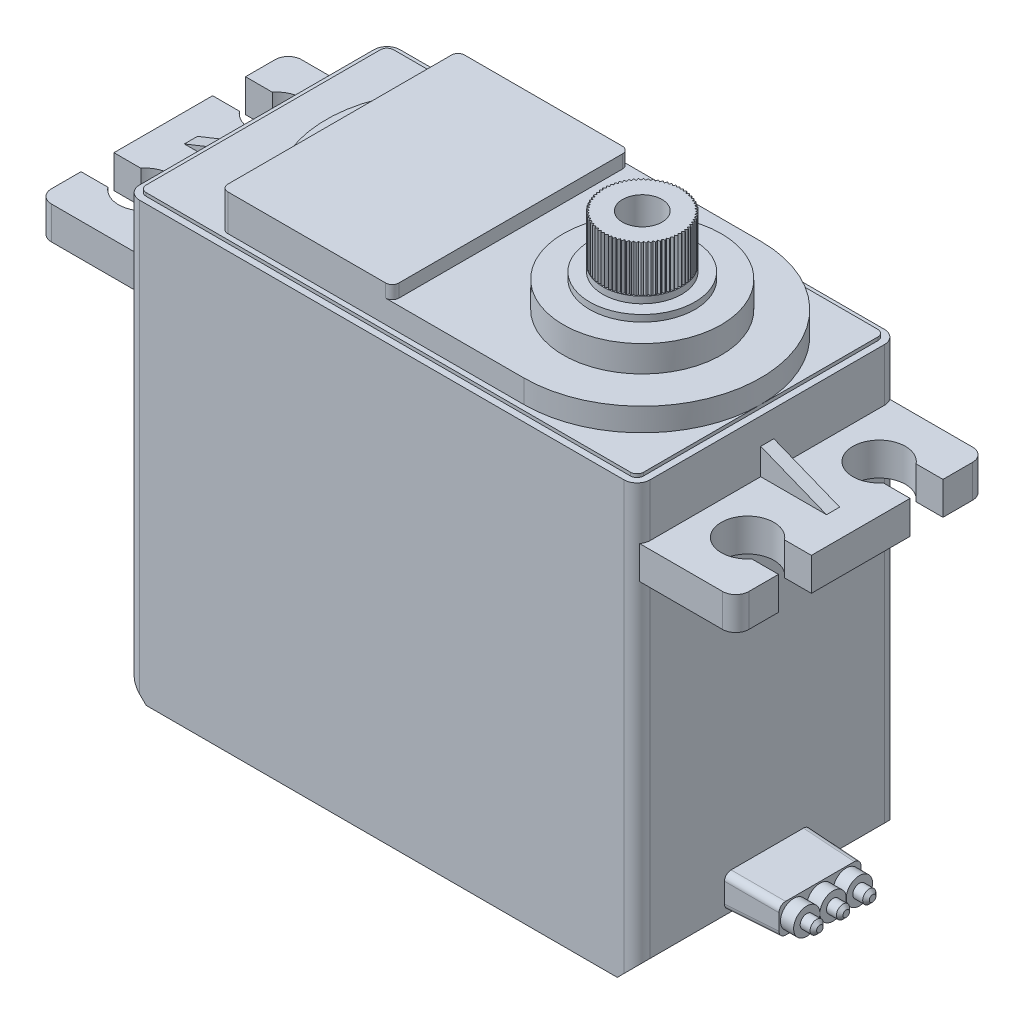
SolidWorks part; units mm, degrees
ref_plane "Front Plane" through (0, 0, 0) normal (0, 0, 1) x (1, 0, 0)
ref_plane "Top Plane" through (0, 0, 0) normal (0, 1, 0) x (1, 0, 0)
ref_plane "Right Plane" through (0, 0, 0) normal (1, 0, 0) x (0, 0, -1)
sketch "Sketch1" plane through (0, 0, 0) normal (0, 1, 0) x (1, 0, 0)
  line L2 (-19.4, 9.9) -> (-19.4, -9.9)
  line L3 (19.4, 9.9) -> (19.4, -9.9)
  line L4 (-19.4, -9.9) -> (19.4, -9.9)
  line L5 (-19.4, 9.9) -> (19.4, 9.9)
extrude "Extrude1" add sketch "Sketch1" along normal blind 26.5
sketch "Sketch2" plane through (0, 26.5, 0) normal (0, 1, 0) x (-1, 0, 0)
  line L0 (19.4, -9.9) -> (-19.4, -9.9)
  line L1 (-19.4, -9.9) -> (-19.4, -9.5)
  line L2 (24.4612, 6.25) -> (26.5, 6.25)
  line L3 (-26.5, -8.5) -> (-26.5, -6.25)
  line L4 (-19.4, 9.9) -> (19.4, 9.9)
  line L5 (24.4612, -3.75) -> (26.5, -3.75)
  line L6 (-19.4, 9.5) -> (-19.4, 9.9)
  line L7 (24.4612, 3.75) -> (26.5, 3.75)
  line L8 (0, 0) -> (0, 8.5) construction
  line L9 (26.5, 6.25) -> (26.5, 8.5)
  line L10 (24.4612, -6.25) -> (26.5, -6.25)
  line L11 (-19.4, 9.5) -> (-25.5, 9.5)
  line L12 (26.5, -3.75) -> (26.5, 3.75)
  line L13 (-19.4, -9.5) -> (-25.5, -9.5)
  line L14 (19.4, -9.5) -> (25.5, -9.5)
  line L15 (-26.5, -3.75) -> (-26.5, 3.75)
  line L16 (-24.4612, -6.25) -> (-26.5, -6.25)
  line L17 (19.4, 9.5) -> (25.5, 9.5)
  line L18 (-26.5, 6.25) -> (-26.5, 8.5)
  line L19 (-24.4612, 3.75) -> (-26.5, 3.75)
  line L20 (19.4, 9.5) -> (19.4, 9.9)
  line L21 (26.5, -8.5) -> (26.5, -6.25)
  line L22 (-24.4612, -3.75) -> (-26.5, -3.75)
  line L23 (19.4, -9.9) -> (19.4, -9.5)
  line L24 (0, 0) -> (-10.2456, 0) construction
  line L25 (-24.4612, 6.25) -> (-26.5, 6.25)
  line L26 (-22.9, 5) -> (-26.6668, 5) construction
  line L27 (-26.5, -3.75) -> (-26.5, -6.25) construction
  line L28 (-24.4612, 6.25) -> (-24.4612, 3.75) construction
  arc A0 (25.5, -9.5) -> (26.5, -8.5) centre (25.5, -8.5) ccw
  arc A1 (26.5, 8.5) -> (25.5, 9.5) centre (25.5, 8.5) ccw
  arc A2 (-24.4612, -6.25) -> (-24.4612, -3.75) centre (-22.9, -5) ccw
  arc A3 (-24.4612, 3.75) -> (-24.4612, 6.25) centre (-22.9, 5) ccw
  arc A4 (24.4612, 3.75) -> (24.4612, 6.25) centre (22.9, 5) cw
  arc A5 (24.4612, -6.25) -> (24.4612, -3.75) centre (22.9, -5) cw
  arc A6 (-26.5, 8.5) -> (-25.5, 9.5) centre (-25.5, 8.5) cw
  arc A7 (-25.5, -9.5) -> (-26.5, -8.5) centre (-25.5, -8.5) cw
  dimension "D5" = 2.5
  dimension "D1" = 53
  dimension "D3" = 10
  dimension "D4" = 2
  dimension "D7" = 1
  dimension "D2" = 3.6
  dimension "D6" = 19
chamfer "Chamfer1" distance 1.5 angle 45 2 edges at (-19.4, 0, 0) (19.4, 0, 0)
extrude "Extrude5" add sketch "Sketch2" along normal blind 2.5
sketch "Sketch3" plane through (0, 29, 0) normal (0, 1, 0) x (-1, 0, 0)
  line L0 (19.4, -9.9) -> (-19.4, -9.9)
  line L1 (-19.4, -9.9) -> (-19.4, 9.9)
  line L2 (-19.4, 9.9) -> (19.4, 9.9)
  line L3 (19.4, 9.9) -> (19.4, -9.9)
extrude "Extrude6" add sketch "Sketch3" along normal blind 4
fillet "Fillet1" radius 1 4 edges at (-19.4, 17.25, -9.9) (19.4, 17.25, -9.9) (-19.4, 17.25, 9.9) (19.4, 17.25, 9.9)
sketch "Sketch5" plane through (0, 33, 0) normal (0, 1, 0) x (-1, 0, 0)
  line L3 (13.1, -8.5) -> (13.1, 8.5)
  line L4 (12.6, 9) -> (-9.9, 9)
  line L5 (12.6, -9) -> (-9.9, -9)
  arc A3 (12.6, 9) -> (13.1, 8.5) centre (12.6, 8.5) cw
  arc A4 (-9.9, 9) -> (-9.9, -9) centre (-9.9, 0) ccw
  arc A5 (13.1, -8.5) -> (12.6, -9) centre (12.6, -8.5) cw
extrude "Extrude8" add sketch "Sketch5" along normal blind 2
sketch "Sketch6" plane through (0, 35, 0) normal (0, 1, 0) x (-1, 0, 0)
  line L6 (0.6, -9) -> (12.6, -9)
  line L7 (13.1, -8.5) -> (13.1, 8.5)
  line L8 (0.6, 9) -> (12.6, 9)
  line L9 (0.1, -8.5) -> (0.1, 8.5)
  arc A0 (13.1, -8.5) -> (12.6, -9) centre (12.6, -8.5) cw
  arc A1 (0.1, -8.5) -> (0.6, -9) centre (0.6, -8.5) ccw
  arc A2 (13.1, 8.5) -> (12.6, 9) centre (12.6, 8.5) ccw
  arc A3 (0.1, 8.5) -> (0.6, 9) centre (0.6, 8.5) cw
  dimension "D1" = 0.5
extrude "Extrude9" add sketch "Sketch6" along normal blind 1
sketch "Sketch7" plane through (0, 33, 0) normal (0, 1, 0) x (-1, 0, 0)
  line L0 (12.6, -5) -> (12.6, 5)
  arc A0 (12.6, -5) -> (12.6, 5) centre (5.1167, 0) ccw
extrude "Extrude10" add sketch "Sketch7" along normal blind 2.5
sketch "Sketch8" plane through (0, 33, 0) normal (0, 1, 0) x (-1, 0, 0)
  line L4 (18.9, -8.9) -> (18.9, 8.9)
  line L5 (18.4, 9.4) -> (-18.4, 9.4)
  line L6 (-18.9, -8.9) -> (-18.9, 8.9)
  line L7 (18.4, -9.4) -> (-18.4, -9.4)
  arc A4 (18.4, 9.4) -> (18.9, 8.9) centre (18.4, 8.9) cw
  arc A5 (-18.9, 8.9) -> (-18.4, 9.4) centre (-18.4, 8.9) cw
  arc A6 (-18.4, -9.4) -> (-18.9, -8.9) centre (-18.4, -8.9) cw
  arc A7 (18.9, -8.9) -> (18.4, -9.4) centre (18.4, -8.9) cw
extrude "Extrude11" add sketch "Sketch8" along normal blind 0.25
sketch "Sketch9" plane through (0, 35, 0) normal (0, 1, 0) x (-1, 0, 0)
  circle A0 centre (-9.9, 0) radius 6
extrude "Extrude12" add sketch "Sketch9" along normal blind 2
sketch "Sketch10" plane through (0, 37, 0) normal (0, 1, 0) x (-1, 0, 0)
  circle A0 centre (-9.9, 0) radius 4
extrude "Extrude13" add sketch "Sketch10" along normal blind 0.5
sketch "Sketch11" plane through (0, 37.5, 0) normal (0, 1, 0) x (-1, 0, 0)
  circle A0 centre (-9.9, 0) radius 3
extrude "Extrude14" add sketch "Sketch11" along normal blind 4 separate body
sketch "Sketch22" plane through (19.4, 0, 0) normal (1, 0, 0) x (0, 0, -1)
  line L0 (-2, 3) -> (2, 3) construction
  circle A0 centre (-2, 3) radius 1
  circle A1 centre (0, 3) radius 1
  circle A2 centre (2, 3) radius 1
  circle A4 centre (0, 3) radius 0.5
  circle A5 centre (2, 3) radius 0.5
  circle A6 centre (-2, 3) radius 0.5
  point P3 (2.8313, 3.8338)
  point P4 (0, 3.5414)
  point P6 (-0.9187, 3.8338)
  point P7 (2, 3.5414)
  point P15 (0.9563, 3.8338)
  dimension "D1" = 1
  dimension "D2" = 0.5
  dimension "D3" = 3
extrude "Extrude25" add sketch "Sketch22" along normal blind 5 separate body
sketch "Sketch24" plane through (19.4, 0, 0) normal (1, 0, 0) x (0, 0, -1)
  circle A0 centre (-2, 3) radius 0.5 construction
  circle A1 centre (0, 3) radius 0.5 construction
  circle A2 centre (2, 3) radius 0.5 construction
  circle A3 centre (-2, 3) radius 0.5
  circle A4 centre (0, 3) radius 0.5
  circle A5 centre (2, 3) radius 0.5
extrude "Extrude26" add sketch "Sketch24" along normal blind 6
chamfer "Chamfer2" distance 0.25 angle 45 3 edges at (25.4, 3, 1.5) (25.4, 3, -0.5) (25.4, 3, -2.5)
sketch "Sketch25" plane through (19.4, 0, 0) normal (1, 0, 0) x (0, 0, -1)
  line L1 (-3.25, 1.75) -> (3.25, 1.75)
  line L2 (-3.25, 1.75) -> (-3.25, 4.25)
  line L3 (-3.25, 4.25) -> (3.25, 4.25)
  line L4 (3.25, 1.75) -> (3.25, 4.25)
  line L5 (-3.25, 1.75) -> (3.25, 4.25) construction
  line L6 (-3.25, 4.25) -> (3.25, 1.75) construction
  circle A0 centre (-2, 3) radius 0.5 construction
  point P0 (0, 3)
  dimension "D1" = 1.25
  dimension "D2" = 1.25
extrude "Extrude27" add sketch "Sketch25" along normal blind 4 draft 2 separate body
fillet "Fillet8" radius 0.5 4 edges at (21.4, 1.8198, 3.1802) (21.4, 1.8198, -3.1802) (21.4, 4.1802, -3.1802) (21.4, 4.1802, 3.1802)
hole_wizard "Ø3.0 (3) Diameter Hole1" positions "Sketch27" profile "Sketch26" hole size "Ø3.0" standard "Ansi Metric"
sketch "Sketch27" plane through (0, 41.5, 0) normal (0, 1, 0) x (-1, 0, 0)
  circle A0 centre (-9.9, 0) radius 3 construction
  point P0 (-9.9, 0)
sketch "Sketch26" plane through (9.9, 41.5, 0) normal (1, 0, 0) x (0, 0, 1)
  line L0 (0, 0) -> (0, 5.9013)
  line L1 (0, 5.9013) -> (1.5, 5)
  line L2 (1.5, 5) -> (1.5, 0)
  line L5 (1.5, 0) -> (0, 0)
  line L10 (0, 5.9013) -> (-1.5, 5) construction
  line L11 (0, -6.35) -> (0, 107.95) construction
  dimension "Hole Dia." = 3
  dimension "Hole Depth" = 5
  dimension "Drill Angle" = 118
sketch "Sketch28" plane through (0, 0, 0) normal (0, 0, 1) x (1, 0, 0)
  line L0 (-24.4, 29) -> (-19.4, 31)
  line L1 (-25.5, 29) -> (-19.2, 29) construction
  line L2 (-19.4, 29) -> (-19.4, 33) construction
  dimension "D1" = 5
  dimension "D2" = 2
rib "Rib2" sketch "Sketch28" sketch "Sketch28" thickness 1 extrusion direction parallel to sketch draft on no parameters "D1"=1
mirror "Mirror1" about plane through (0, 0, 0) normal (1, 0, 0) of "Rib2"
sketch "Sketch30" plane through (0, 41.5, 0) normal (0, 1, 0) x (1, 0, 0)
  line L0 (9.775, 2.9974) -> (9.9, 2.85)
  line L1 (9.9, 2.85) -> (10.025, 2.9974)
  line L2 (9.9, 2.85) -> (9.9, 3) construction
  line L3 (10.1555, 2.8385) -> (10.2932, 2.9741)
  line L4 (10.0442, 2.9965) -> (10.1555, 2.8385)
  line L5 (10.4089, 2.8042) -> (10.5582, 2.9269)
  line L6 (10.3122, 2.9715) -> (10.4089, 2.8042)
  line L7 (10.6582, 2.7473) -> (10.8179, 2.8561)
  line L8 (10.5769, 2.9226) -> (10.6582, 2.7473)
  line L9 (10.9014, 2.6683) -> (11.0702, 2.7623)
  line L10 (10.8362, 2.8502) -> (10.9014, 2.6683)
  line L11 (11.1366, 2.5678) -> (11.3131, 2.6463)
  line L12 (11.0879, 2.7548) -> (11.1366, 2.5678)
  line L13 (11.3618, 2.4466) -> (11.5447, 2.509)
  line L14 (11.3301, 2.6372) -> (11.3618, 2.4466)
  line L15 (11.5752, 2.3057) -> (11.763, 2.3515)
  line L16 (11.5607, 2.4984) -> (11.5752, 2.3057)
  line L17 (11.7751, 2.1463) -> (11.9662, 2.175)
  line L18 (11.778, 2.3395) -> (11.7751, 2.1463)
  line L19 (11.96, 1.9695) -> (12.1529, 1.981)
  line L20 (11.9801, 2.1617) -> (11.96, 1.9695)
  line L21 (12.1282, 1.7769) -> (12.3214, 1.7711)
  line L22 (12.1655, 1.9666) -> (12.1282, 1.7769)
  line L23 (12.2785, 1.5701) -> (12.4704, 1.5469)
  line L24 (12.3327, 1.7556) -> (12.2785, 1.5701)
  line L25 (12.4097, 1.3505) -> (12.5987, 1.3103)
  line L26 (12.4803, 1.5304) -> (12.4097, 1.3505)
  line L27 (12.5207, 1.1201) -> (12.7053, 1.0631)
  line L28 (12.6071, 1.293) -> (12.5207, 1.1201)
  line L29 (12.6105, 0.8807) -> (12.7893, 0.8074)
  line L30 (12.7121, 1.0451) -> (12.6105, 0.8807)
  line L31 (12.6785, 0.6342) -> (12.8501, 0.5451)
  line L32 (12.7944, 0.7888) -> (12.6785, 0.6342)
  line L33 (12.7242, 0.3826) -> (12.887, 0.2785)
  line L34 (12.8535, 0.5262) -> (12.7242, 0.3826)
  line L35 (12.7471, 0.1279) -> (12.9, 0.0096)
  line L36 (12.8888, 0.2594) -> (12.7471, 0.1279)
  line L37 (12.7471, -0.1279) -> (12.8888, -0.2594)
  line L38 (12.9, -0.0096) -> (12.7471, -0.1279)
  line L39 (12.7242, -0.3826) -> (12.8535, -0.5262)
  line L40 (12.887, -0.2785) -> (12.7242, -0.3826)
  line L41 (12.6785, -0.6342) -> (12.7944, -0.7888)
  line L42 (12.8501, -0.5451) -> (12.6785, -0.6342)
  line L43 (12.6105, -0.8807) -> (12.7121, -1.0451)
  line L44 (12.7893, -0.8074) -> (12.6105, -0.8807)
  line L45 (12.5207, -1.1201) -> (12.6071, -1.293)
  line L46 (12.7053, -1.0631) -> (12.5207, -1.1201)
  line L47 (12.4097, -1.3505) -> (12.4803, -1.5304)
  line L48 (12.5987, -1.3103) -> (12.4097, -1.3505)
  line L49 (12.2785, -1.5701) -> (12.3327, -1.7556)
  line L50 (12.4704, -1.5469) -> (12.2785, -1.5701)
  line L51 (12.1282, -1.7769) -> (12.1655, -1.9666)
  line L52 (12.3214, -1.7711) -> (12.1282, -1.7769)
  line L53 (11.96, -1.9695) -> (11.9801, -2.1617)
  line L54 (12.1529, -1.981) -> (11.96, -1.9695)
  line L55 (11.7751, -2.1463) -> (11.778, -2.3395)
  line L56 (11.9662, -2.175) -> (11.7751, -2.1463)
  line L57 (11.5752, -2.3057) -> (11.5607, -2.4984)
  line L58 (11.763, -2.3515) -> (11.5752, -2.3057)
  line L59 (11.3618, -2.4466) -> (11.3301, -2.6372)
  line L60 (11.5447, -2.509) -> (11.3618, -2.4466)
  line L61 (11.1366, -2.5678) -> (11.0879, -2.7548)
  line L62 (11.3131, -2.6463) -> (11.1366, -2.5678)
  line L63 (10.9014, -2.6683) -> (10.8362, -2.8502)
  line L64 (11.0702, -2.7623) -> (10.9014, -2.6683)
  line L65 (10.6582, -2.7473) -> (10.5769, -2.9226)
  line L66 (10.8179, -2.8561) -> (10.6582, -2.7473)
  line L67 (10.4089, -2.8042) -> (10.3122, -2.9715)
  line L68 (10.5582, -2.9269) -> (10.4089, -2.8042)
  line L69 (10.1555, -2.8385) -> (10.0442, -2.9965)
  line L70 (10.2932, -2.9741) -> (10.1555, -2.8385)
  line L71 (9.9, -2.85) -> (9.775, -2.9974)
  line L72 (10.025, -2.9974) -> (9.9, -2.85)
  line L73 (9.6445, -2.8385) -> (9.5068, -2.9741)
  line L74 (9.7558, -2.9965) -> (9.6445, -2.8385)
  line L75 (9.3911, -2.8042) -> (9.2418, -2.9269)
  line L76 (9.4878, -2.9715) -> (9.3911, -2.8042)
  line L77 (9.1418, -2.7473) -> (8.9821, -2.8561)
  line L78 (9.2231, -2.9226) -> (9.1418, -2.7473)
  line L79 (8.8986, -2.6683) -> (8.7298, -2.7623)
  line L80 (8.9638, -2.8502) -> (8.8986, -2.6683)
  line L81 (8.6634, -2.5678) -> (8.4869, -2.6463)
  line L82 (8.7121, -2.7548) -> (8.6634, -2.5678)
  line L83 (8.4382, -2.4466) -> (8.2553, -2.509)
  line L84 (8.4699, -2.6372) -> (8.4382, -2.4466)
  line L85 (8.2248, -2.3057) -> (8.037, -2.3515)
  line L86 (8.2393, -2.4984) -> (8.2248, -2.3057)
  line L87 (8.0249, -2.1463) -> (7.8338, -2.175)
  line L88 (8.022, -2.3395) -> (8.0249, -2.1463)
  line L89 (7.84, -1.9695) -> (7.6471, -1.981)
  line L90 (7.8199, -2.1617) -> (7.84, -1.9695)
  line L91 (7.6718, -1.7769) -> (7.4786, -1.7711)
  line L92 (7.6345, -1.9666) -> (7.6718, -1.7769)
  line L93 (7.5215, -1.5701) -> (7.3296, -1.5469)
  line L94 (7.4673, -1.7556) -> (7.5215, -1.5701)
  line L95 (7.3903, -1.3505) -> (7.2013, -1.3103)
  line L96 (7.3197, -1.5304) -> (7.3903, -1.3505)
  line L97 (7.2793, -1.1201) -> (7.0947, -1.0631)
  line L98 (7.1929, -1.293) -> (7.2793, -1.1201)
  line L99 (7.1895, -0.8807) -> (7.0107, -0.8074)
  line L100 (7.0879, -1.0451) -> (7.1895, -0.8807)
  line L101 (7.1215, -0.6342) -> (6.9499, -0.5451)
  line L102 (7.0056, -0.7888) -> (7.1215, -0.6342)
  line L103 (7.0758, -0.3826) -> (6.913, -0.2785)
  line L104 (6.9465, -0.5262) -> (7.0758, -0.3826)
  line L105 (7.0529, -0.1279) -> (6.9, -0.0096)
  line L106 (6.9112, -0.2594) -> (7.0529, -0.1279)
  line L107 (7.0529, 0.1279) -> (6.9112, 0.2594)
  line L108 (6.9, 0.0096) -> (7.0529, 0.1279)
  line L109 (7.0758, 0.3826) -> (6.9465, 0.5262)
  line L110 (6.913, 0.2785) -> (7.0758, 0.3826)
  line L111 (7.1215, 0.6342) -> (7.0056, 0.7888)
  line L112 (6.9499, 0.5451) -> (7.1215, 0.6342)
  line L113 (7.1895, 0.8807) -> (7.0879, 1.0451)
  line L114 (7.0107, 0.8074) -> (7.1895, 0.8807)
  line L115 (7.2793, 1.1201) -> (7.1929, 1.293)
  line L116 (7.0947, 1.0631) -> (7.2793, 1.1201)
  line L117 (7.3903, 1.3505) -> (7.3197, 1.5304)
  line L118 (7.2013, 1.3103) -> (7.3903, 1.3505)
  line L119 (7.5215, 1.5701) -> (7.4673, 1.7556)
  line L120 (7.3296, 1.5469) -> (7.5215, 1.5701)
  line L121 (7.6718, 1.7769) -> (7.6345, 1.9666)
  line L122 (7.4786, 1.7711) -> (7.6718, 1.7769)
  line L123 (7.84, 1.9695) -> (7.8199, 2.1617)
  line L124 (7.6471, 1.981) -> (7.84, 1.9695)
  line L125 (8.0249, 2.1463) -> (8.022, 2.3395)
  line L126 (7.8338, 2.175) -> (8.0249, 2.1463)
  line L127 (8.2248, 2.3057) -> (8.2393, 2.4984)
  line L128 (8.037, 2.3515) -> (8.2248, 2.3057)
  line L129 (8.4382, 2.4466) -> (8.4699, 2.6372)
  line L130 (8.2553, 2.509) -> (8.4382, 2.4466)
  line L131 (8.6634, 2.5678) -> (8.7121, 2.7548)
  line L132 (8.4869, 2.6463) -> (8.6634, 2.5678)
  line L133 (8.8986, 2.6683) -> (8.9638, 2.8502)
  line L134 (8.7298, 2.7623) -> (8.8986, 2.6683)
  line L135 (9.1418, 2.7473) -> (9.2231, 2.9226)
  line L136 (8.9821, 2.8561) -> (9.1418, 2.7473)
  line L137 (9.3911, 2.8042) -> (9.4878, 2.9715)
  line L138 (9.2418, 2.9269) -> (9.3911, 2.8042)
  line L139 (9.6445, 2.8385) -> (9.7558, 2.9965)
  line L140 (9.5068, 2.9741) -> (9.6445, 2.8385)
  circle A0 centre (9.9, 0) radius 3 construction
  arc A1 (10.025, 2.9974) -> (9.775, 2.9974) centre (9.9, 0) ccw
  arc A2 (10.2932, 2.9741) -> (10.0442, 2.9965) centre (9.9, 0) ccw
  arc A3 (10.5582, 2.9269) -> (10.3122, 2.9715) centre (9.9, 0) ccw
  arc A4 (10.8179, 2.8561) -> (10.5769, 2.9226) centre (9.9, 0) ccw
  arc A5 (11.0702, 2.7623) -> (10.8362, 2.8502) centre (9.9, 0) ccw
  arc A6 (11.3131, 2.6463) -> (11.0879, 2.7548) centre (9.9, 0) ccw
  arc A7 (11.5447, 2.509) -> (11.3301, 2.6372) centre (9.9, 0) ccw
  arc A8 (11.763, 2.3515) -> (11.5607, 2.4984) centre (9.9, 0) ccw
  arc A9 (11.9662, 2.175) -> (11.778, 2.3395) centre (9.9, 0) ccw
  arc A10 (12.1529, 1.981) -> (11.9801, 2.1617) centre (9.9, 0) ccw
  arc A11 (12.3214, 1.7711) -> (12.1655, 1.9666) centre (9.9, 0) ccw
  arc A12 (12.4704, 1.5469) -> (12.3327, 1.7556) centre (9.9, 0) ccw
  arc A13 (12.5987, 1.3103) -> (12.4803, 1.5304) centre (9.9, 0) ccw
  arc A14 (12.7053, 1.0631) -> (12.6071, 1.293) centre (9.9, 0) ccw
  arc A15 (12.7893, 0.8074) -> (12.7121, 1.0451) centre (9.9, 0) ccw
  arc A16 (12.8501, 0.5451) -> (12.7944, 0.7888) centre (9.9, 0) ccw
  arc A17 (12.887, 0.2785) -> (12.8535, 0.5262) centre (9.9, 0) ccw
  arc A18 (12.9, 0.0096) -> (12.8888, 0.2594) centre (9.9, 0) ccw
  arc A19 (12.8888, -0.2594) -> (12.9, -0.0096) centre (9.9, 0) ccw
  arc A20 (12.8535, -0.5262) -> (12.887, -0.2785) centre (9.9, 0) ccw
  arc A21 (12.7944, -0.7888) -> (12.8501, -0.5451) centre (9.9, 0) ccw
  arc A22 (12.7121, -1.0451) -> (12.7893, -0.8074) centre (9.9, 0) ccw
  arc A23 (12.6071, -1.293) -> (12.7053, -1.0631) centre (9.9, 0) ccw
  arc A24 (12.4803, -1.5304) -> (12.5987, -1.3103) centre (9.9, 0) ccw
  arc A25 (12.3327, -1.7556) -> (12.4704, -1.5469) centre (9.9, 0) ccw
  arc A26 (12.1655, -1.9666) -> (12.3214, -1.7711) centre (9.9, 0) ccw
  arc A27 (11.9801, -2.1617) -> (12.1529, -1.981) centre (9.9, 0) ccw
  arc A28 (11.778, -2.3395) -> (11.9662, -2.175) centre (9.9, 0) ccw
  arc A29 (11.5607, -2.4984) -> (11.763, -2.3515) centre (9.9, 0) ccw
  arc A30 (11.3301, -2.6372) -> (11.5447, -2.509) centre (9.9, 0) ccw
  arc A31 (11.0879, -2.7548) -> (11.3131, -2.6463) centre (9.9, 0) ccw
  arc A32 (10.8362, -2.8502) -> (11.0702, -2.7623) centre (9.9, 0) ccw
  arc A33 (10.5769, -2.9226) -> (10.8179, -2.8561) centre (9.9, 0) ccw
  arc A34 (10.3122, -2.9715) -> (10.5582, -2.9269) centre (9.9, 0) ccw
  arc A35 (10.0442, -2.9965) -> (10.2932, -2.9741) centre (9.9, 0) ccw
  arc A36 (9.775, -2.9974) -> (10.025, -2.9974) centre (9.9, 0) ccw
  arc A37 (9.5068, -2.9741) -> (9.7558, -2.9965) centre (9.9, 0) ccw
  arc A38 (9.2418, -2.9269) -> (9.4878, -2.9715) centre (9.9, 0) ccw
  arc A39 (8.9821, -2.8561) -> (9.2231, -2.9226) centre (9.9, 0) ccw
  arc A40 (8.7298, -2.7623) -> (8.9638, -2.8502) centre (9.9, 0) ccw
  arc A41 (8.4869, -2.6463) -> (8.7121, -2.7548) centre (9.9, 0) ccw
  arc A42 (8.2553, -2.509) -> (8.4699, -2.6372) centre (9.9, 0) ccw
  arc A43 (8.037, -2.3515) -> (8.2393, -2.4984) centre (9.9, 0) ccw
  arc A44 (7.8338, -2.175) -> (8.022, -2.3395) centre (9.9, 0) ccw
  arc A45 (7.6471, -1.981) -> (7.8199, -2.1617) centre (9.9, 0) ccw
  arc A46 (7.4786, -1.7711) -> (7.6345, -1.9666) centre (9.9, 0) ccw
  arc A47 (7.3296, -1.5469) -> (7.4673, -1.7556) centre (9.9, 0) ccw
  arc A48 (7.2013, -1.3103) -> (7.3197, -1.5304) centre (9.9, 0) ccw
  arc A49 (7.0947, -1.0631) -> (7.1929, -1.293) centre (9.9, 0) ccw
  arc A50 (7.0107, -0.8074) -> (7.0879, -1.0451) centre (9.9, 0) ccw
  arc A51 (6.9499, -0.5451) -> (7.0056, -0.7888) centre (9.9, 0) ccw
  arc A52 (6.913, -0.2785) -> (6.9465, -0.5262) centre (9.9, 0) ccw
  arc A53 (6.9, -0.0096) -> (6.9112, -0.2594) centre (9.9, 0) ccw
  arc A54 (6.9112, 0.2594) -> (6.9, 0.0096) centre (9.9, 0) ccw
  arc A55 (6.9465, 0.5262) -> (6.913, 0.2785) centre (9.9, 0) ccw
  arc A56 (7.0056, 0.7888) -> (6.9499, 0.5451) centre (9.9, 0) ccw
  arc A57 (7.0879, 1.0451) -> (7.0107, 0.8074) centre (9.9, 0) ccw
  arc A58 (7.1929, 1.293) -> (7.0947, 1.0631) centre (9.9, 0) ccw
  arc A59 (7.3197, 1.5304) -> (7.2013, 1.3103) centre (9.9, 0) ccw
  arc A60 (7.4673, 1.7556) -> (7.3296, 1.5469) centre (9.9, 0) ccw
  arc A61 (7.6345, 1.9666) -> (7.4786, 1.7711) centre (9.9, 0) ccw
  arc A62 (7.8199, 2.1617) -> (7.6471, 1.981) centre (9.9, 0) ccw
  arc A63 (8.022, 2.3395) -> (7.8338, 2.175) centre (9.9, 0) ccw
  arc A64 (8.2393, 2.4984) -> (8.037, 2.3515) centre (9.9, 0) ccw
  arc A65 (8.4699, 2.6372) -> (8.2553, 2.509) centre (9.9, 0) ccw
  arc A66 (8.7121, 2.7548) -> (8.4869, 2.6463) centre (9.9, 0) ccw
  arc A67 (8.9638, 2.8502) -> (8.7298, 2.7623) centre (9.9, 0) ccw
  arc A68 (9.2231, 2.9226) -> (8.9821, 2.8561) centre (9.9, 0) ccw
  arc A69 (9.4878, 2.9715) -> (9.2418, 2.9269) centre (9.9, 0) ccw
  arc A70 (9.7558, 2.9965) -> (9.5068, 2.9741) centre (9.9, 0) ccw
  dimension "D1" = 0.25
  dimension "D2" = 0.15
  dimension "D3" = 70
extrude "Cut-Extrude1" cut sketch "Sketch30" against normal blind 3.5
